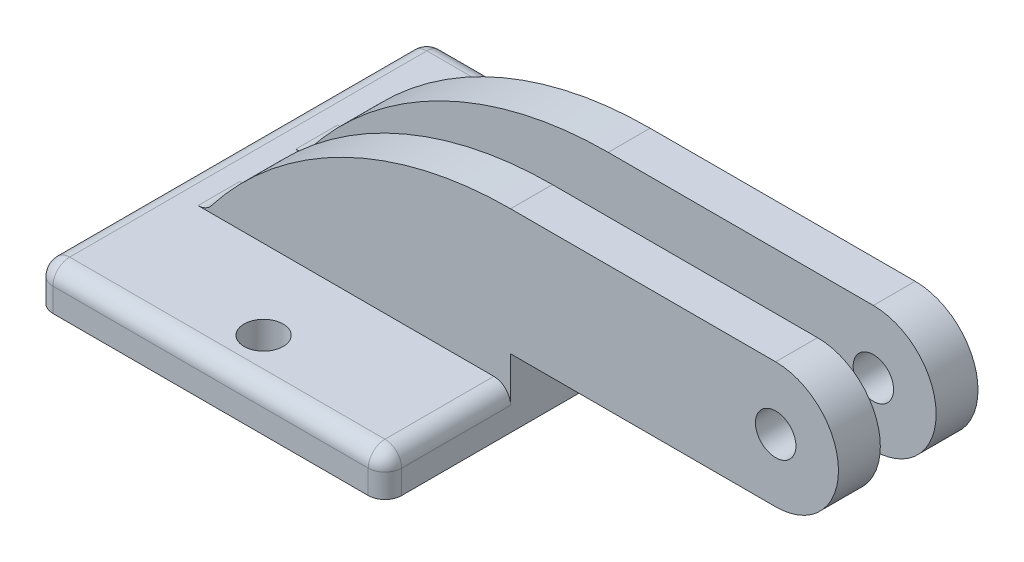
SolidWorks part; units mm, degrees
ref_plane "Front Plane" through (0, 0, 0) normal (0, 0, 1) x (1, 0, 0)
ref_plane "Top Plane" through (0, 0, 0) normal (0, 1, 0) x (1, 0, 0)
ref_plane "Right Plane" through (0, 0, 0) normal (1, 0, 0) x (0, 0, -1)
sketch "Sketch1" plane through (0, 0, 0) normal (0, 1, 0) x (1, 0, 0)
  line L0 (0, 0) -> (0.3175, 6.7945) construction
  line L1 (-7.9375, 8.89) -> (7.9375, 8.89)
  line L2 (-7.9375, 8.89) -> (-7.9375, -8.89)
  line L3 (-7.9375, -8.89) -> (7.9375, -8.89)
  line L4 (7.9375, 8.89) -> (7.9375, -8.89)
  line L5 (0.3175, -6.7945) -> (0, 0) construction
  circle A0 centre (0.3175, 6.7945) radius 0.889
  circle A1 centre (0.3175, -6.7945) radius 0.889
  point P4 (0, 8.89)
  point P5 (-7.9375, 0)
  dimension "D3" = 1.778
  dimension "D4" = 1.778
  dimension "D5" = 7.62
  dimension "D1" = 17.78
  dimension "D2" = 15.875
  dimension "D6" = 2.0955
extrude "Boss-Extrude1" add sketch "Sketch1" along normal blind 1.8415
sketch "Sketch2" plane through (0, 0, 0) normal (0, 0, 1) x (1, 0, 0)
  line L0 (-7.9375, 1.8415) -> (7.9375, 1.8415) construction
  line L1 (-7.9375, 1.8415) -> (7.9375, 1.8415)
  line L2 (7.9375, 1.8415) -> (7.9375, 3.1115)
  line L3 (7.9375, 3.1115) -> (20.0025, 3.1115)
  line L4 (20.0025, 8.8265) -> (7.9375, 8.8265)
  arc A0 (20.0025, 3.1115) -> (20.0025, 8.8265) centre (20.0025, 5.969) ccw
  circle A2 centre (20.0025, 5.969) radius 0.9207
  arc A3 (7.9375, 8.8265) -> (-5.9055, 1.8415) centre (7.9375, -8.3832) ccw
  dimension "D1" = 1.27
  dimension "D4" = 1.8415
  dimension "D5" = 2.032
  dimension "D2" = 5.715
  dimension "D3" = 12.065
extrude "Boss-Extrude2" add sketch "Sketch2" along normal mid plane 6.35 contours L4 A3 L1 L2 L3 A0 A2 region at (9.2396, 5.3798, 0)
extrude "Cut-Extrude1" cut sketch "Sketch2<2>" against normal mid plane 2.54 contours L4 A3 L1 L2 L3 A0 A2 region at (9.2396, 5.3798, 0)
sketch "Sketch2<2>" plane through (0, 0, 0) normal (0, 0, 1) x (1, 0, 0) same geometry as "Sketch2"
fillet "Fillet1" radius 0.762 11 edges at (7.9375, 0.9207, -8.89) (-7.9375, 0.9207, -8.89) (7.9375, 0.9207, 8.89) (-7.9375, 0.9207, 8.89) (-5.9055, 1.8415, -2.2225) (-5.9055, 1.8415, 2.2225) (7.9375, 1.8415, -6.0325) (0, 1.8415, -8.89) (0, 1.8415, 8.89) (7.9375, 1.8415, 6.0325) (-7.9375, 1.8415, 0)
